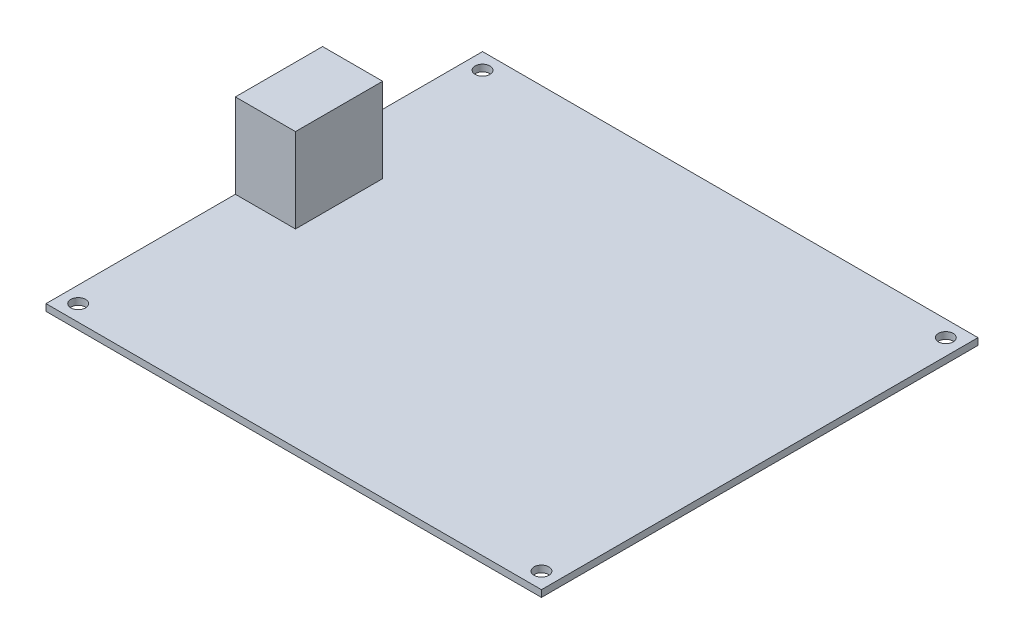
SolidWorks part; units mm, degrees
ref_plane "Front Plane" through (0, 0, 0) normal (0, 0, 1) x (1, 0, 0)
ref_plane "Top Plane" through (0, 0, 0) normal (0, 1, 0) x (1, 0, 0)
ref_plane "Right Plane" through (0, 0, 0) normal (1, 0, 0) x (0, 0, -1)
sketch "Sketch1" plane through (0, 0, 0) normal (0, 1, 0) x (1, 0, 0)
  line L0 (0, 51.7525) -> (117.475, 51.7525) construction
  line L1 (0, 0) -> (117.475, 0)
  line L2 (0, 0) -> (0, 103.505)
  line L3 (0, 103.505) -> (117.475, 103.505)
  line L4 (117.475, 0) -> (117.475, 103.505)
  circle A0 centre (3.815, 3.815) radius 1.7526
  circle A1 centre (113.66, 3.815) radius 1.7526
  circle A2 centre (113.66, 99.69) radius 1.7526
  circle A3 centre (3.815, 99.69) radius 1.7526
  point P11 (0, 0)
  dimension "D3" = 3.5052
  dimension "D1" = 117.475
  dimension "D2" = 103.505
  dimension "D4" = 3.815
  dimension "D5" = 3.815
  dimension "D6" = 3.815
extrude "Boss-Extrude1" add sketch "Sketch1" along normal blind 1.6
sketch "Sketch2" plane through (0, 1.6, 0) normal (0, 1, 0) x (1, 0, 0)
  line L0 (0, 103.505) -> (0, 0) construction
  line L1 (0, 65.577) -> (14.25, 65.577)
  line L2 (0, 65.577) -> (0, 44.901)
  line L3 (0, 44.901) -> (14.25, 44.901)
  line L4 (14.25, 65.577) -> (14.25, 44.901)
  point P6 (0, 55.239)
  dimension "D1" = 48.266
  dimension "D2" = 20.676
  dimension "D3" = 14.25
extrude "Boss-Extrude2" add sketch "Sketch2" along normal blind 20
